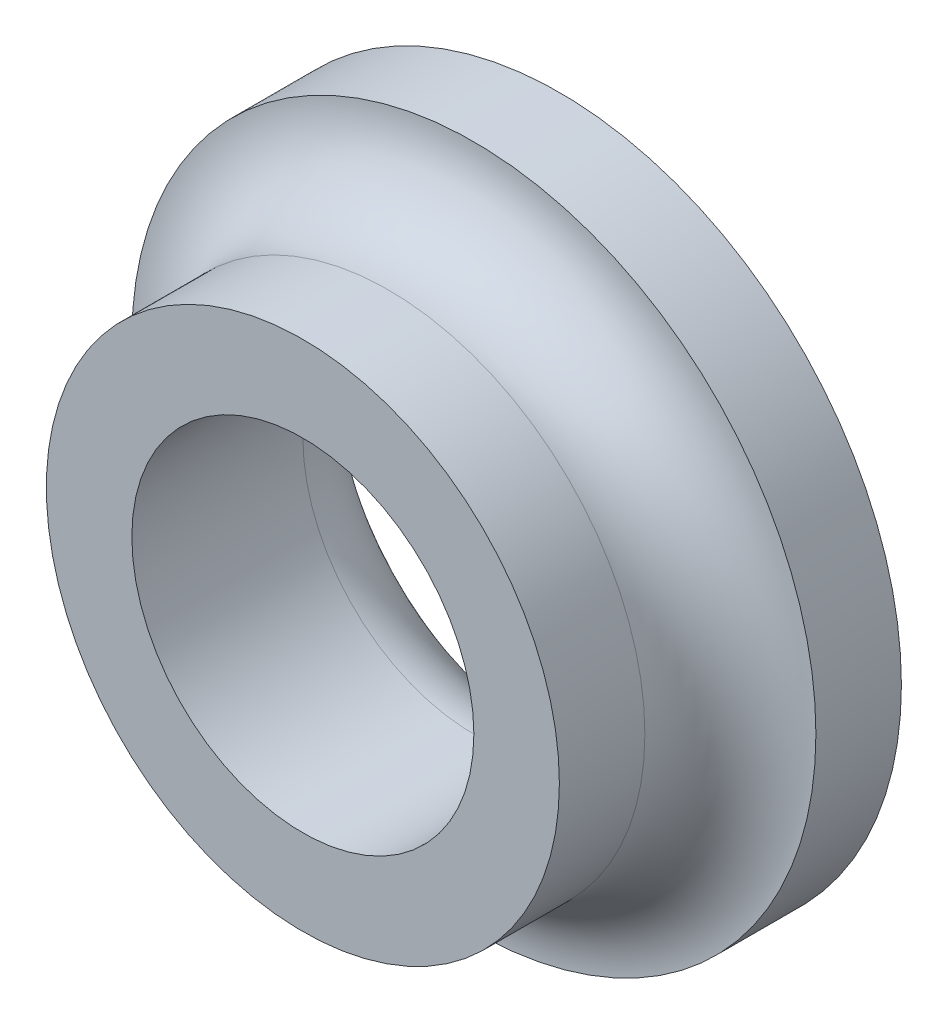
SolidWorks part; units mm, degrees
material "PE High Density"
ref_plane "Front" through (0, 0, 0) normal (0, 0, 1) x (1, 0, 0)
ref_plane "Top" through (0, 0, 0) normal (0, 1, 0) x (1, 0, 0)
ref_plane "Right" through (0, 0, 0) normal (1, 0, 0) x (0, 0, -1)
sketch "Sketch1" plane through (0, 0, 0) normal (0, 0, 1) x (1, 0, 0)
  circle A0 centre (0, 0) radius 4
extrude "Boss-Extrude1" add sketch "Sketch1" along normal blind 1
sketch "Sketch2" plane through (0, 0, 1) normal (0, 0, 1) x (1, 0, 0)
  circle A0 centre (0, 0) radius 3
extrude "Boss-Extrude2" add sketch "Sketch2" along normal blind 2
fillet "Fillet1" radius 1 1 edges at (3, 0, 1)
sketch "Sketch3" plane through (0, 0, 3) normal (0, 0, 1) x (1, 0, 0)
  circle A0 centre (0, 0) radius 2
extrude "Cut-Extrude1" cut sketch "Sketch3" against normal blind 4
fillet "Fillet2" radius 1 1 edges at (2, 0, 0)
